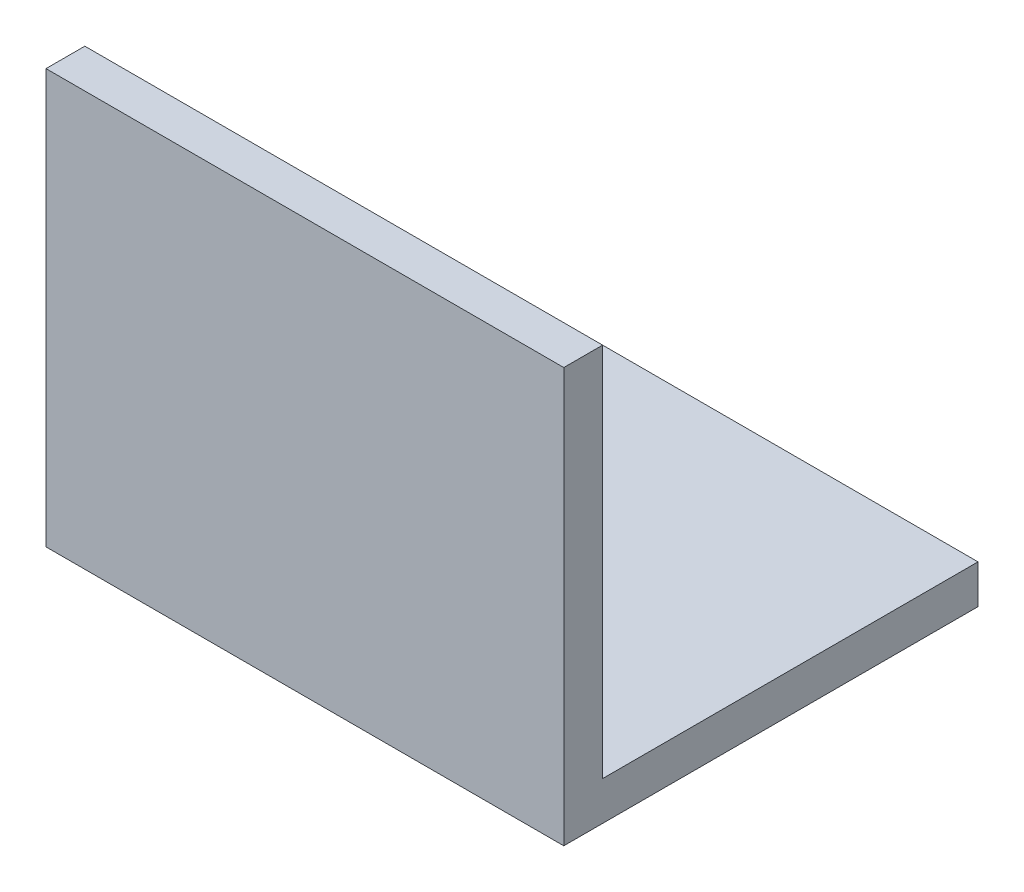
SolidWorks part; units mm, degrees
ref_plane "Спереди" through (0, 0, 0) normal (0, 0, 1) x (1, 0, 0)
ref_plane "Сверху" through (0, 0, 0) normal (0, 1, 0) x (1, 0, 0)
ref_plane "Справа" through (0, 0, 0) normal (1, 0, 0) x (0, 0, -1)
sketch "Эскиз1" plane through (0, 0, 0) normal (1, 0, 0) x (0, 0, -1)
  line L0 (0, 32) -> (0, 0)
  line L1 (0, 0) -> (32, 0)
extrude "Вытянуть-Тонкостенный1" add sketch "Эскиз1" along normal blind 40 thin thin type one direction reverse wall 3
